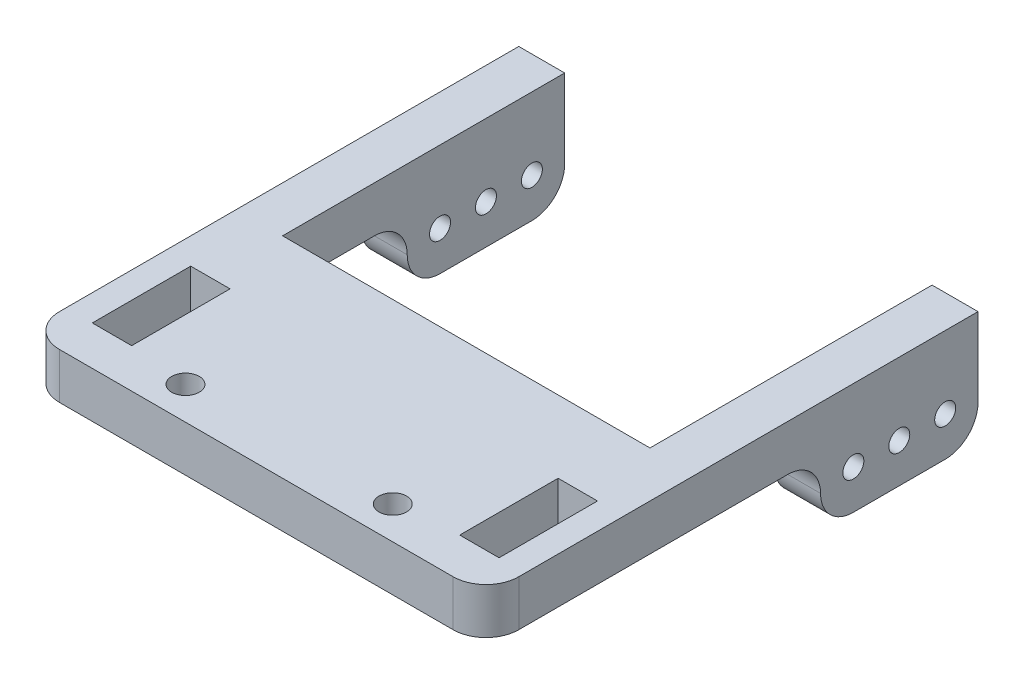
SolidWorks part; units mm, degrees
ref_plane "Front" through (0, 0, 0) normal (0, 0, 1) x (1, 0, 0)
ref_plane "Top" through (0, 0, 0) normal (0, 1, 0) x (1, 0, 0)
ref_plane "Right" through (0, 0, 0) normal (1, 0, 0) x (0, 0, -1)
sketch "草图1" plane through (0, 0, 0) normal (0, 1, 0) x (1, 0, 0)
  line L0 (7, -43) -> (63, -43)
  line L1 (0, 0) -> (7, 0)
  line L2 (0, 0) -> (0, -75)
  line L3 (0, -75) -> (70, -75)
  line L4 (70, 0) -> (70, -75)
  line L5 (35, -1043) -> (35, 48957) construction
  line L6 (63, -43) -> (63, 0)
  line L8 (60, -54) -> (66, -54)
  line L9 (7, -43) -> (7, 0)
  line L11 (63, 0) -> (70, 0)
  line L12 (60, -54) -> (60, -69)
  line L13 (60, -69) -> (66, -69)
  line L14 (66, -54) -> (66, -69)
  line L15 (60, -54) -> (66, -69) construction
  line L16 (60, -69) -> (66, -54) construction
  line L17 (10, -69) -> (4, -54) construction
  line L18 (10, -54) -> (4, -69) construction
  line L19 (4, -54) -> (4, -69)
  line L20 (10, -69) -> (4, -69)
  line L21 (10, -54) -> (10, -69)
  line L22 (10, -54) -> (4, -54)
  point P4 (63, -61.5)
  point P14 (35, -43)
  point P21 (7, -61.5)
  dimension "D1" = 75
  dimension "D2" = 70
  dimension "D3" = 56
  dimension "D4" = 7
  dimension "D5" = 32
  dimension "D6" = 4
  dimension "D7" = 6
  dimension "D8" = 15
extrude "凸台-拉伸1" add sketch "草图1" along normal blind 7
sketch "草图2" plane through (0, 0, 0) normal (0, -1, 0) x (1, 0, 0)
  line L0 (7, 43) -> (7, 0) construction
  line L1 (0, 0) -> (7, 0)
  line L2 (0, 0) -> (0, 24)
  line L3 (0, 24) -> (7, 24)
  line L4 (7, 0) -> (7, 24)
  line L5 (70, 75) -> (70, 0) construction
  line L6 (63, 0) -> (70, 0)
  line L7 (63, 0) -> (63, 24)
  line L8 (63, 24) -> (70, 24)
  line L9 (70, 0) -> (70, 24)
  dimension "D1" = 24
  dimension "D2" = 24
extrude "凸台-拉伸2" add sketch "草图2" along normal blind 10
sketch "草图3" plane through (70, 0, 0) normal (1, 0, 0) x (0, 0, -1)
  line L0 (0, -10) -> (-24, -10) construction
  circle A0 centre (-12, -4) radius 1.6
  circle A1 centre (-19, -4) radius 1.6
  circle A2 centre (-5, -4) radius 1.6
  point P10 (-12, -10)
  dimension "D1" = 3.2
  dimension "D2" = 3.2
  dimension "D3" = 3.2
  dimension "D4" = 7
  dimension "D6" = 6
  dimension "D5" = 7
extrude "切除-拉伸1" cut sketch "草图3" against normal through all
sketch "草图7" plane through (0, 7, 0) normal (0, 1, 0) x (1, 0, 0)
  line L0 (35, -1059.5735) -> (35, 48940.4265) construction
  line L1 (0, -75) -> (70, -75) construction
  circle A0 centre (19.2, -70) radius 2.1
  circle A1 centre (50.8, -70) radius 2.1
  point P6 (35, -75)
  dimension "D2" = 4.2
  dimension "D3" = 15.8
  dimension "D1" = 5
extrude "切除-拉伸2" cut sketch "草图7" against normal up to next
fillet "圆角1" radius 5 8 edges at (70, 3.5, 75) (0, 3.5, 75) (66.5, -10, 24) (66.5, 0, 24) (66.5, -10, 0) (3.5, -10, 0) (3.5, -10, 24) (3.5, 0, 24)
